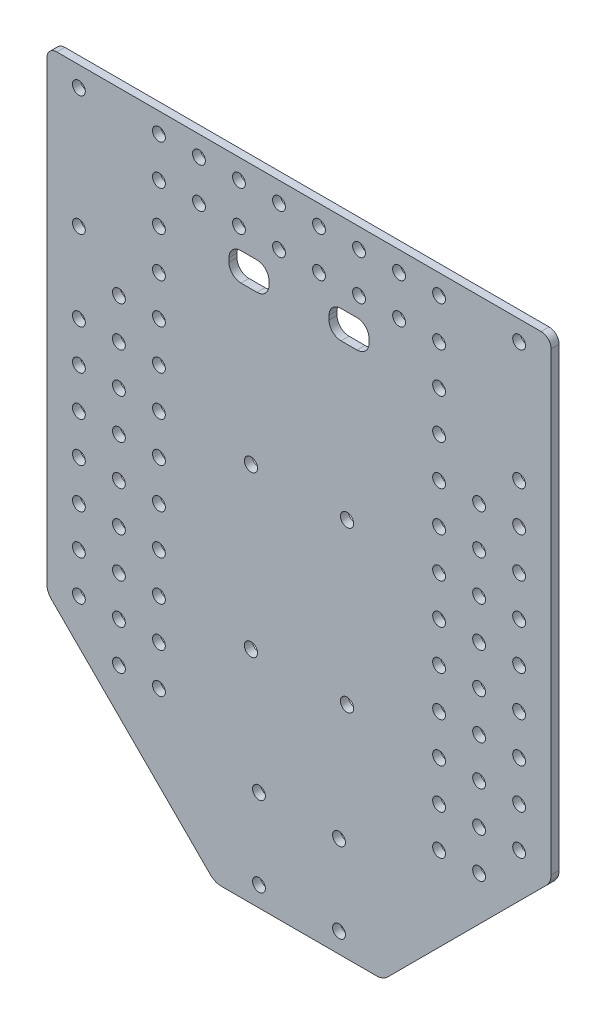
SolidWorks part; units mm, degrees
ref_plane "Front" through (0, 0, 0) normal (0, 0, 1) x (1, 0, 0)
ref_plane "Top" through (0, 0, 0) normal (0, 1, 0) x (1, 0, 0)
ref_plane "Right" through (0, 0, 0) normal (1, 0, 0) x (0, 0, -1)
sketch "Эскиз1" plane through (0, 0, 0) normal (0, 0, 1) x (1, 0, 0)
  line L0 (-63, 0) -> (63, 0)
  line L1 (63, 0) -> (63, -160)
  line L3 (63, -160) -> (-63, -160)
  line L5 (-63, -160) -> (-63, 0)
  point P3 (0, 0)
  point P7 (0, -160)
  dimension "D1" = 126
  dimension "D2" = 160
extrude "Пластина нижняя" add sketch "Эскиз1" along normal blind 2
sketch "Эскиз2" plane through (0, 0, 2) normal (0, 0, 1) x (1, 0, 0)
  line L14 (10, -135) -> (-10, -135) construction
  line L15 (10, -135) -> (10, -155) construction
  line L16 (10, -155) -> (-10, -155) construction
  line L17 (-10, -135) -> (-10, -155) construction
  line L18 (-63, -160) -> (63, -160) construction
  circle A8 centre (10, -135) radius 1.6
  circle A9 centre (-10, -135) radius 1.6
  circle A10 centre (-10, -155) radius 1.6
  circle A11 centre (10, -155) radius 1.6
  point P7 (0, -135)
  dimension "D4" = 3.2
  dimension "D2" = 20
  dimension "D3" = 5
extrude "Крепление_заднего_колеса" cut sketch "Эскиз2" against normal up to next
sketch "Эскиз3" plane through (0, 0, 0) normal (0, 0, -1) x (-1, 0, 0)
  line L1 (-12, -65) -> (12, -65) construction
  line L2 (-12, -65) -> (-12, -105) construction
  line L3 (-12, -105) -> (12, -105) construction
  line L4 (12, -65) -> (12, -105) construction
  line L5 (63, -160) -> (-63, -160) construction
  circle A0 centre (-12, -65) radius 1.65
  circle A1 centre (12, -65) radius 1.65
  circle A2 centre (12, -105) radius 1.65
  circle A3 centre (-12, -105) radius 1.65
  point P8 (0, -65)
  dimension "D3" = 3.3
  dimension "D1" = 40
  dimension "D2" = 24
  dimension "D4" = 55
extrude "Крепление батареи" cut sketch "Эскиз3" against normal through all
chamfer "Фаска2" distance 42 1 edges at (-63, -160, 1)
chamfer "Фаска1" distance 42 1 edges at (63, -160, 1)
fillet "Скругление1" radius 4 4 edges at (63, -118, 1) (-63, -118, 1) (-21, -160, 1) (21, -160, 1)
sketch "Эскиз6" plane through (0, 0, 0) normal (0, 0, -1) x (-1, 0, 0)
  line L0 (-63, 0) -> (63, 0) construction
  line L1 (-17.5, -20) -> (-7.5, -20)
  line L2 (-17.5, -20) -> (-17.5, -27)
  line L3 (-17.5, -27) -> (-7.5, -27)
  line L4 (-7.5, -20) -> (-7.5, -27)
  line L5 (0, 0) -> (0, -160) construction
  line L6 (19.3431, -160) -> (-19.3431, -160) construction
  line L7 (7.5, -20) -> (7.5, -27)
  line L8 (17.5, -27) -> (7.5, -27)
  line L9 (17.5, -20) -> (17.5, -27)
  line L10 (17.5, -20) -> (7.5, -20)
  dimension "D1" = 7
  dimension "D2" = 10
  dimension "D3" = 20
  dimension "D4" = 7.5
extrude "Под провода двигателей" cut sketch "Эскиз6" against normal through all
sketch "Эскиз4" plane through (0, 0, 0) normal (0, 0, -1) x (-1, 0, 0)
  line L0 (0, 0) -> (0, -160) construction
  line L1 (-63, 0) -> (63, 0) construction
  line L2 (19.3431, -160) -> (-19.3431, -160) construction
  circle A0 centre (5, -155) radius 1.6 construction
  circle A2 centre (15, -155) radius 1.6 construction
  circle A3 centre (25, -155) radius 1.6 construction
  circle A4 centre (35, -155) radius 1.6 construction
  circle A5 centre (45, -155) radius 1.6 construction
  circle A6 centre (55, -155) radius 1.6 construction
  circle A7 centre (65, -155) radius 1.6 construction
  circle A8 centre (-65, -155) radius 1.6 construction
  circle A9 centre (-55, -155) radius 1.6 construction
  circle A10 centre (-45, -155) radius 1.6 construction
  circle A11 centre (-35, -155) radius 1.6 construction
  circle A12 centre (-25, -155) radius 1.6 construction
  circle A13 centre (-15, -155) radius 1.6 construction
  circle A14 centre (-5, -155) radius 1.6 construction
  circle A15 centre (5, -145) radius 1.6 construction
  circle A16 centre (15, -145) radius 1.6 construction
  circle A17 centre (25, -145) radius 1.6 construction
  circle A18 centre (35, -145) radius 1.6 construction
  circle A19 centre (45, -145) radius 1.6 construction
  circle A20 centre (55, -145) radius 1.6 construction
  circle A21 centre (65, -145) radius 1.6 construction
  circle A22 centre (-65, -145) radius 1.6 construction
  circle A23 centre (-55, -145) radius 1.6 construction
  circle A24 centre (-45, -145) radius 1.6 construction
  circle A25 centre (-35, -145) radius 1.6 construction
  circle A26 centre (-25, -145) radius 1.6 construction
  circle A27 centre (-15, -145) radius 1.6 construction
  circle A28 centre (-5, -145) radius 1.6 construction
  circle A29 centre (5, -135) radius 1.6 construction
  circle A30 centre (15, -135) radius 1.6 construction
  circle A31 centre (25, -135) radius 1.6 construction
  circle A32 centre (35, -135) radius 1.6 construction
  circle A33 centre (45, -135) radius 1.6 construction
  circle A34 centre (55, -135) radius 1.6 construction
  circle A35 centre (65, -135) radius 1.6 construction
  circle A36 centre (-65, -135) radius 1.6 construction
  circle A37 centre (-55, -135) radius 1.6 construction
  circle A38 centre (-45, -135) radius 1.6 construction
  circle A39 centre (-35, -135) radius 1.6 construction
  circle A40 centre (-25, -135) radius 1.6 construction
  circle A41 centre (-15, -135) radius 1.6 construction
  circle A42 centre (-5, -135) radius 1.6 construction
  circle A43 centre (5, -125) radius 1.6 construction
  circle A44 centre (15, -125) radius 1.6 construction
  circle A45 centre (25, -125) radius 1.6 construction
  circle A46 centre (35, -125) radius 1.6
  circle A47 centre (45, -125) radius 1.6
  circle A48 centre (55, -125) radius 1.6 construction
  circle A49 centre (65, -125) radius 1.6 construction
  circle A50 centre (-65, -125) radius 1.6 construction
  circle A51 centre (-55, -125) radius 1.6 construction
  circle A52 centre (-45, -125) radius 1.6
  circle A53 centre (-35, -125) radius 1.6
  circle A54 centre (-25, -125) radius 1.6 construction
  circle A55 centre (-15, -125) radius 1.6 construction
  circle A56 centre (-5, -125) radius 1.6 construction
  circle A57 centre (5, -115) radius 1.6 construction
  circle A58 centre (15, -115) radius 1.6 construction
  circle A59 centre (25, -115) radius 1.6 construction
  circle A60 centre (35, -115) radius 1.6
  circle A61 centre (45, -115) radius 1.6
  circle A62 centre (55, -115) radius 1.6
  circle A63 centre (65, -115) radius 1.6 construction
  circle A64 centre (-65, -115) radius 1.6 construction
  circle A65 centre (-55, -115) radius 1.6
  circle A66 centre (-45, -115) radius 1.6
  circle A67 centre (-35, -115) radius 1.6
  circle A68 centre (-25, -115) radius 1.6 construction
  circle A69 centre (-15, -115) radius 1.6 construction
  circle A70 centre (-5, -115) radius 1.6 construction
  circle A71 centre (5, -105) radius 1.6 construction
  circle A72 centre (15, -105) radius 1.6 construction
  circle A73 centre (25, -105) radius 1.6 construction
  circle A74 centre (35, -105) radius 1.6
  circle A75 centre (45, -105) radius 1.6
  circle A76 centre (55, -105) radius 1.6
  circle A77 centre (65, -105) radius 1.6 construction
  circle A78 centre (-65, -105) radius 1.6 construction
  circle A79 centre (-55, -105) radius 1.6
  circle A80 centre (-45, -105) radius 1.6
  circle A81 centre (-35, -105) radius 1.6
  circle A82 centre (-25, -105) radius 1.6 construction
  circle A83 centre (-15, -105) radius 1.6 construction
  circle A84 centre (-5, -105) radius 1.6 construction
  circle A85 centre (5, -95) radius 1.6 construction
  circle A86 centre (15, -95) radius 1.6 construction
  circle A87 centre (25, -95) radius 1.6 construction
  circle A88 centre (35, -95) radius 1.6
  circle A89 centre (45, -95) radius 1.6
  circle A90 centre (55, -95) radius 1.6
  circle A91 centre (65, -95) radius 1.6 construction
  circle A92 centre (-65, -95) radius 1.6 construction
  circle A93 centre (-55, -95) radius 1.6
  circle A94 centre (-45, -95) radius 1.6
  circle A95 centre (-35, -95) radius 1.6
  circle A96 centre (-25, -95) radius 1.6 construction
  circle A97 centre (-15, -95) radius 1.6 construction
  circle A98 centre (-5, -95) radius 1.6 construction
  circle A99 centre (5, -85) radius 1.6 construction
  circle A100 centre (15, -85) radius 1.6 construction
  circle A101 centre (25, -85) radius 1.6 construction
  circle A102 centre (35, -85) radius 1.6
  circle A103 centre (45, -85) radius 1.6
  circle A104 centre (55, -85) radius 1.6
  circle A105 centre (65, -85) radius 1.6 construction
  circle A106 centre (-65, -85) radius 1.6 construction
  circle A107 centre (-55, -85) radius 1.6
  circle A108 centre (-45, -85) radius 1.6
  circle A109 centre (-35, -85) radius 1.6
  circle A110 centre (-25, -85) radius 1.6 construction
  circle A111 centre (-15, -85) radius 1.6 construction
  circle A112 centre (-5, -85) radius 1.6 construction
  circle A113 centre (5, -75) radius 1.6 construction
  circle A114 centre (15, -75) radius 1.6 construction
  circle A115 centre (25, -75) radius 1.6 construction
  circle A116 centre (35, -75) radius 1.6
  circle A117 centre (45, -75) radius 1.6
  circle A118 centre (55, -75) radius 1.6
  circle A119 centre (65, -75) radius 1.6 construction
  circle A120 centre (-65, -75) radius 1.6 construction
  circle A121 centre (-55, -75) radius 1.6
  circle A122 centre (-45, -75) radius 1.6
  circle A123 centre (-35, -75) radius 1.6
  circle A124 centre (-25, -75) radius 1.6 construction
  circle A125 centre (-15, -75) radius 1.6 construction
  circle A126 centre (-5, -75) radius 1.6 construction
  circle A127 centre (5, -65) radius 1.6 construction
  circle A128 centre (15, -65) radius 1.6 construction
  circle A129 centre (25, -65) radius 1.6 construction
  circle A130 centre (35, -65) radius 1.6
  circle A131 centre (45, -65) radius 1.6
  circle A132 centre (55, -65) radius 1.6
  circle A133 centre (65, -65) radius 1.6 construction
  circle A134 centre (-65, -65) radius 1.6 construction
  circle A135 centre (-55, -65) radius 1.6
  circle A136 centre (-45, -65) radius 1.6
  circle A137 centre (-35, -65) radius 1.6
  circle A138 centre (-25, -65) radius 1.6 construction
  circle A139 centre (-15, -65) radius 1.6 construction
  circle A140 centre (-5, -65) radius 1.6 construction
  circle A141 centre (5, -55) radius 1.6 construction
  circle A142 centre (15, -55) radius 1.6 construction
  circle A143 centre (25, -55) radius 1.6 construction
  circle A144 centre (35, -55) radius 1.6
  circle A145 centre (45, -55) radius 1.6
  circle A146 centre (55, -55) radius 1.6
  circle A147 centre (65, -55) radius 1.6 construction
  circle A148 centre (-65, -55) radius 1.6 construction
  circle A149 centre (-55, -55) radius 1.6
  circle A150 centre (-45, -55) radius 1.6
  circle A151 centre (-35, -55) radius 1.6
  circle A152 centre (-25, -55) radius 1.6 construction
  circle A153 centre (-15, -55) radius 1.6 construction
  circle A154 centre (-5, -55) radius 1.6 construction
  circle A155 centre (5, -45) radius 1.6 construction
  circle A156 centre (15, -45) radius 1.6 construction
  circle A157 centre (25, -45) radius 1.6 construction
  circle A158 centre (35, -45) radius 1.6
  circle A159 centre (45, -45) radius 1.6
  circle A160 centre (55, -45) radius 1.6 construction
  circle A161 centre (65, -45) radius 1.6 construction
  circle A162 centre (-65, -45) radius 1.6 construction
  circle A163 centre (-55, -45) radius 1.6
  circle A164 centre (-45, -45) radius 1.6
  circle A165 centre (-35, -45) radius 1.6
  circle A166 centre (-25, -45) radius 1.6 construction
  circle A167 centre (-15, -45) radius 1.6 construction
  circle A168 centre (-5, -45) radius 1.6 construction
  circle A169 centre (5, -35) radius 1.6 construction
  circle A170 centre (15, -35) radius 1.6 construction
  circle A171 centre (25, -35) radius 1.6 construction
  circle A172 centre (35, -35) radius 1.6
  circle A173 centre (45, -35) radius 1.6 construction
  circle A174 centre (55, -35) radius 1.6
  circle A175 centre (65, -35) radius 1.6 construction
  circle A176 centre (-65, -35) radius 1.6 construction
  circle A177 centre (-55, -35) radius 1.6
  circle A178 centre (-45, -35) radius 1.6 construction
  circle A179 centre (-35, -35) radius 1.6
  circle A180 centre (-25, -35) radius 1.6 construction
  circle A181 centre (-15, -35) radius 1.6 construction
  circle A182 centre (-5, -35) radius 1.6 construction
  circle A183 centre (5, -25) radius 1.6 construction
  circle A184 centre (15, -25) radius 1.6 construction
  circle A185 centre (25, -25) radius 1.6 construction
  circle A186 centre (35, -25) radius 1.6
  circle A187 centre (45, -25) radius 1.6 construction
  circle A188 centre (55, -25) radius 1.6 construction
  circle A189 centre (65, -25) radius 1.6 construction
  circle A190 centre (-65, -25) radius 1.6 construction
  circle A191 centre (-55, -25) radius 1.6 construction
  circle A192 centre (-45, -25) radius 1.6 construction
  circle A193 centre (-35, -25) radius 1.6
  circle A194 centre (-25, -25) radius 1.6 construction
  circle A195 centre (-15, -25) radius 1.6 construction
  circle A196 centre (-5, -25) radius 1.6 construction
  circle A197 centre (5, -15) radius 1.6
  circle A198 centre (15, -15) radius 1.6
  circle A199 centre (25, -15) radius 1.6
  circle A200 centre (35, -15) radius 1.6
  circle A201 centre (45, -15) radius 1.6 construction
  circle A202 centre (55, -15) radius 1.6 construction
  circle A203 centre (65, -15) radius 1.6 construction
  circle A204 centre (-65, -15) radius 1.6 construction
  circle A205 centre (-55, -15) radius 1.6 construction
  circle A206 centre (-45, -15) radius 1.6 construction
  circle A207 centre (-35, -15) radius 1.6
  circle A208 centre (-25, -15) radius 1.6
  circle A209 centre (-15, -15) radius 1.6
  circle A210 centre (-5, -15) radius 1.6
  circle A211 centre (5, -5) radius 1.6
  circle A212 centre (15, -5) radius 1.6
  circle A213 centre (25, -5) radius 1.6
  circle A214 centre (35, -5) radius 1.6
  circle A215 centre (45, -5) radius 1.6 construction
  circle A216 centre (55, -5) radius 1.6
  circle A217 centre (65, -5) radius 1.6 construction
  circle A218 centre (-65, -5) radius 1.6 construction
  circle A219 centre (-55, -5) radius 1.6
  circle A220 centre (-45, -5) radius 1.6 construction
  circle A221 centre (-35, -5) radius 1.6
  circle A222 centre (-25, -5) radius 1.6
  circle A223 centre (-15, -5) radius 1.6
  circle A224 centre (-5, -5) radius 1.6
  circle A225 centre (5, 5) radius 1.6 construction
  circle A226 centre (15, 5) radius 1.6 construction
  circle A227 centre (25, 5) radius 1.6 construction
  circle A228 centre (35, 5) radius 1.6 construction
  circle A229 centre (45, 5) radius 1.6 construction
  circle A230 centre (55, 5) radius 1.6 construction
  circle A231 centre (65, 5) radius 1.6 construction
  circle A232 centre (-65, 5) radius 1.6 construction
  circle A233 centre (-55, 5) radius 1.6 construction
  circle A234 centre (-45, 5) radius 1.6 construction
  circle A235 centre (-35, 5) radius 1.6 construction
  circle A236 centre (-25, 5) radius 1.6 construction
  circle A237 centre (-15, 5) radius 1.6 construction
  circle A238 centre (-5, 5) radius 1.6 construction
  circle A239 centre (5, 15) radius 1.6 construction
  circle A240 centre (15, 15) radius 1.6 construction
  circle A241 centre (25, 15) radius 1.6 construction
  circle A242 centre (35, 15) radius 1.6 construction
  circle A243 centre (45, 15) radius 1.6 construction
  circle A244 centre (55, 15) radius 1.6 construction
  circle A245 centre (65, 15) radius 1.6 construction
  circle A246 centre (-65, 15) radius 1.6 construction
  circle A247 centre (-55, 15) radius 1.6 construction
  circle A248 centre (-45, 15) radius 1.6 construction
  circle A249 centre (-35, 15) radius 1.6 construction
  circle A250 centre (-25, 15) radius 1.6 construction
  circle A251 centre (-15, 15) radius 1.6 construction
  circle A252 centre (-5, 15) radius 1.6 construction
  circle A253 centre (5, 25) radius 1.6 construction
  circle A254 centre (15, 25) radius 1.6 construction
  circle A255 centre (25, 25) radius 1.6 construction
  circle A256 centre (35, 25) radius 1.6 construction
  circle A257 centre (45, 25) radius 1.6 construction
  circle A258 centre (55, 25) radius 1.6 construction
  circle A259 centre (65, 25) radius 1.6 construction
  circle A260 centre (-65, 25) radius 1.6 construction
  circle A261 centre (-55, 25) radius 1.6 construction
  circle A262 centre (-45, 25) radius 1.6 construction
  circle A263 centre (-35, 25) radius 1.6 construction
  circle A264 centre (-25, 25) radius 1.6 construction
  circle A265 centre (-15, 25) radius 1.6 construction
  circle A266 centre (-5, 25) radius 1.6 construction
  circle A267 centre (5, 35) radius 1.6 construction
  circle A268 centre (15, 35) radius 1.6 construction
  circle A269 centre (25, 35) radius 1.6 construction
  circle A270 centre (35, 35) radius 1.6 construction
  circle A271 centre (45, 35) radius 1.6 construction
  circle A272 centre (55, 35) radius 1.6 construction
  circle A273 centre (65, 35) radius 1.6 construction
  circle A274 centre (-65, 35) radius 1.6 construction
  circle A275 centre (-55, 35) radius 1.6 construction
  circle A276 centre (-45, 35) radius 1.6 construction
  circle A277 centre (-35, 35) radius 1.6 construction
  circle A278 centre (-25, 35) radius 1.6 construction
  circle A279 centre (-15, 35) radius 1.6 construction
  circle A280 centre (-5, 35) radius 1.6 construction
  circle A281 centre (5, 45) radius 1.6 construction
  circle A282 centre (15, 45) radius 1.6 construction
  circle A283 centre (25, 45) radius 1.6 construction
  circle A284 centre (35, 45) radius 1.6 construction
  circle A285 centre (45, 45) radius 1.6 construction
  circle A286 centre (55, 45) radius 1.6 construction
  circle A287 centre (65, 45) radius 1.6 construction
  circle A288 centre (-65, 45) radius 1.6 construction
  circle A289 centre (-55, 45) radius 1.6 construction
  circle A290 centre (-45, 45) radius 1.6 construction
  circle A291 centre (-35, 45) radius 1.6 construction
  circle A292 centre (-25, 45) radius 1.6 construction
  circle A293 centre (-15, 45) radius 1.6 construction
  circle A294 centre (-5, 45) radius 1.6 construction
  point P34 (0, 0)
  dimension "D1" = 5
  dimension "D3" = 3.2
  dimension "D2" = 5
  dimension "D5" = 10
  dimension "D7" = 10
  dimension "D4" = 7
  dimension "D6" = 21
extrude "Сетка отв 10х10" cut sketch "Эскиз4" against normal through all
fillet "Скругление2" radius 3 8 edges at (7.5, -27, 1) (7.5, -20, 1) (17.5, -27, 1) (17.5, -20, 1) (-7.5, -27, 1) (-17.5, -27, 1) (-17.5, -20, 1) (-7.5, -20, 1)
fillet "Скругление3" radius 2.5 2 edges at (63, 0, 1) (-63, 0, 1)
